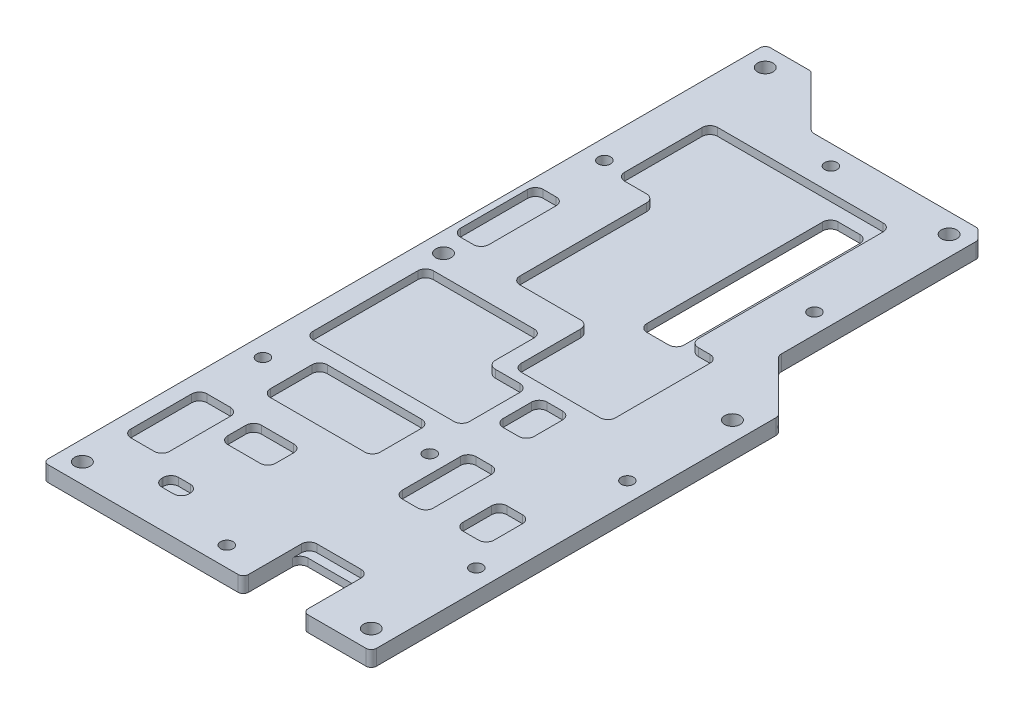
SolidWorks part; units mm, degrees
ref_plane "Front Plane" through (0, 0, 0) normal (0, 0, 1) x (1, 0, 0)
ref_plane "Top Plane" through (0, 0, 0) normal (0, 1, 0) x (1, 0, 0)
ref_plane "Right Plane" through (0, 0, 0) normal (1, 0, 0) x (0, 0, -1)
sketch "Sketch1" plane through (0, 0, 0) normal (0, 1, 0) x (1, 0, 0)
  line L0 (0, 1) -> (0, 138.7)
  line L1 (1, 0) -> (37.75, 0)
  line L2 (63.5, 1) -> (63.5, 78.3258)
  line L3 (1, 139.7) -> (8.4758, 139.7)
  line L4 (19.6713, 129.54) -> (50.8958, 129.54)
  line L5 (9.1829, 139.4071) -> (18.6107, 129.9793)
  line L6 (53.34, 89.5213) -> (53.34, 127.0958)
  line L7 (63.2071, 79.0329) -> (53.7793, 88.4607)
  line L8 (51.6029, 129.2471) -> (53.0471, 127.8029)
  line L13 (38.75, 1) -> (38.75, 9.5)
  line L14 (40.25, 11) -> (48.75, 11)
  line L15 (50.25, 9.5) -> (50.25, 1)
  line L16 (51.25, 0) -> (62.5, 0)
  arc A2 (1, 0) -> (0, 1) centre (1, 1) cw
  arc A3 (63.5, 1) -> (62.5, 0) centre (62.5, 1) cw
  arc A4 (53.7793, 88.4607) -> (53.34, 89.5213) centre (54.84, 89.5213) cw
  arc A5 (18.6107, 129.9793) -> (19.6713, 129.54) centre (19.6713, 131.04) ccw
  arc A6 (63.5, 78.3258) -> (63.2071, 79.0329) centre (62.5, 78.3258) ccw
  arc A7 (53.34, 127.0958) -> (53.0471, 127.8029) centre (52.34, 127.0958) ccw
  arc A8 (51.6029, 129.2471) -> (50.8958, 129.54) centre (50.8958, 128.54) ccw
  arc A9 (9.1829, 139.4071) -> (8.4758, 139.7) centre (8.4758, 138.7) ccw
  arc A10 (1, 139.7) -> (0, 138.7) centre (1, 138.7) ccw
  arc A13 (48.75, 11) -> (50.25, 9.5) centre (48.75, 9.5) cw
  arc A14 (38.75, 9.5) -> (40.25, 11) centre (40.25, 9.5) cw
  arc A15 (50.25, 1) -> (51.25, 0) centre (51.25, 1) ccw
  arc A16 (38.75, 1) -> (37.75, 0) centre (37.75, 1) cw
  point P20 (0, 0)
  point P23 (63.5, 0)
  point P26 (53.34, 88.9)
  point P29 (19.05, 129.54)
  point P32 (63.5, 78.74)
  point P35 (53.34, 127.51)
  point P38 (51.31, 129.54)
  point P41 (8.89, 139.7)
  point P44 (0, 139.7)
  point P45 (38.75, 11)
  point P48 (50.25, 0)
  point P51 (38.75, 0)
  dimension "D14" = 1.5
  dimension "D15" = 1
  dimension "D16" = 1
  dimension "D17" = 1.5
  dimension "D18" = 1
  dimension "D19" = 1
  dimension "D1" = 139.7
  dimension "D2" = 63.5
  dimension "D3" = 78.74
  dimension "D4" = 8.89
  dimension "D5" = 10.16
  dimension "D6" = 10.16
  dimension "D7" = 32.26
  dimension "D8" = 10.16
  dimension "D9" = 10.16
  dimension "D10" = 2.03
  dimension "D11" = 13.25
  dimension "D12" = 11.5
  dimension "D13" = 11
extrude "Boss-Extrude1" add sketch "Sketch1" along normal blind 3
sketch "Sketch2" plane through (0, 3, 0) normal (0, 1, 0) x (1, 0, 0)
  line L36 (50.25, 0) -> (50.25, 11.25)
  line L37 (51.25, 0) -> (62.5, 0) construction
  line L38 (48.75, 12.75) -> (40.25, 12.75)
  line L39 (38.75, 11.25) -> (38.75, 0)
  line L40 (1, 0) -> (37.75, 0) construction
  line L41 (38.75, 0) -> (50.25, 0)
  line L42 (63.5, 1) -> (63.5, 78.3258) construction
  line L43 (0, 138.7) -> (0, 1) construction
  line L44 (52.25, 37.5) -> (55.25, 37.5)
  line L45 (50.75, 36) -> (50.75, 30.5)
  line L46 (52.25, 29) -> (55.25, 29)
  line L47 (56.75, 36) -> (56.75, 30.5)
  line L48 (41, 42.75) -> (44, 42.75)
  line L49 (39.5, 41.25) -> (39.5, 30)
  line L50 (41, 28.5) -> (44, 28.5)
  line L51 (45.5, 41.25) -> (45.5, 30)
  line L52 (11.25, 43.75) -> (29.5, 43.75)
  line L53 (9.75, 42.25) -> (9.75, 34.25)
  line L54 (11.25, 32.75) -> (29.5, 32.75)
  line L55 (31, 42.25) -> (31, 34.25)
  line L56 (18, 10.5) -> (15.75, 10.5)
  line L57 (19.5, 9) -> (19.5, 8.75)
  line L58 (18, 7.25) -> (15.75, 7.25)
  line L59 (14.25, 9) -> (14.25, 8.75)
  line L60 (4.25, 68.25) -> (4.25, 48)
  line L61 (4.5, 27.25) -> (9, 27.25)
  line L62 (3, 25.75) -> (3, 14)
  line L63 (4.5, 12.5) -> (9, 12.5)
  line L64 (10.5, 25.75) -> (10.5, 14)
  line L65 (15, 27.25) -> (21.25, 27.25)
  line L66 (13.5, 25.75) -> (13.5, 22.25)
  line L67 (15, 20.75) -> (21.25, 20.75)
  line L68 (22.75, 25.75) -> (22.75, 22.25)
  line L69 (5.75, 46.5) -> (33, 46.5)
  line L70 (34.5, 48) -> (34.5, 57.75)
  line L71 (33, 59.25) -> (28.25, 59.25)
  line L72 (26.75, 60.75) -> (26.75, 68.25)
  line L73 (25.25, 69.75) -> (5.75, 69.75)
  line L74 (31.25, 61.25) -> (46.5, 61.25)
  line L75 (38.75, 58.75) -> (41.75, 58.75)
  line L76 (37.25, 57.25) -> (37.25, 51.75)
  line L77 (38.75, 50.25) -> (41.75, 50.25)
  line L78 (43.25, 57.25) -> (43.25, 51.75)
  line L79 (48, 62.75) -> (48, 81)
  line L80 (46.5, 82.5) -> (44.25, 82.5)
  line L81 (42.75, 84) -> (42.75, 119.75)
  line L82 (41.25, 121.25) -> (9.25, 121.25)
  line L83 (7.75, 119.75) -> (7.75, 104.75)
  line L84 (9.25, 103.25) -> (13.5, 103.25)
  line L85 (15, 101.75) -> (15, 77.25)
  line L86 (16.5, 75.75) -> (28.25, 75.75)
  line L87 (29.75, 74.25) -> (29.75, 62.75)
  line L89 (2.75, 94) -> (5.25, 94)
  line L90 (1.25, 92.5) -> (1.25, 79.5)
  line L91 (2.75, 78) -> (5.25, 78)
  line L92 (6.75, 92.5) -> (6.75, 79.5)
  arc A32 (50.25, 11.25) -> (48.75, 12.75) centre (48.75, 11.25) ccw
  arc A33 (40.25, 12.75) -> (38.75, 11.25) centre (40.25, 11.25) ccw
  arc A34 (50.75, 30.5) -> (52.25, 29) centre (52.25, 30.5) ccw
  arc A35 (55.25, 29) -> (56.75, 30.5) centre (55.25, 30.5) ccw
  arc A36 (56.75, 36) -> (55.25, 37.5) centre (55.25, 36) ccw
  arc A37 (50.75, 36) -> (52.25, 37.5) centre (52.25, 36) cw
  arc A38 (39.5, 30) -> (41, 28.5) centre (41, 30) ccw
  arc A39 (44, 28.5) -> (45.5, 30) centre (44, 30) ccw
  arc A40 (44, 42.75) -> (45.5, 41.25) centre (44, 41.25) cw
  arc A41 (41, 42.75) -> (39.5, 41.25) centre (41, 41.25) ccw
  arc A42 (29.5, 43.75) -> (31, 42.25) centre (29.5, 42.25) cw
  arc A43 (29.5, 32.75) -> (31, 34.25) centre (29.5, 34.25) ccw
  arc A44 (9.75, 34.25) -> (11.25, 32.75) centre (11.25, 34.25) ccw
  arc A45 (11.25, 43.75) -> (9.75, 42.25) centre (11.25, 42.25) ccw
  arc A46 (19.5, 8.75) -> (18, 7.25) centre (18, 8.75) cw
  arc A47 (18, 10.5) -> (19.5, 9) centre (18, 9) cw
  arc A48 (15.75, 7.25) -> (14.25, 8.75) centre (15.75, 8.75) cw
  arc A49 (15.75, 10.5) -> (14.25, 9) centre (15.75, 9) ccw
  arc A50 (21.25, 20.75) -> (22.75, 22.25) centre (21.25, 22.25) ccw
  arc A51 (21.25, 27.25) -> (22.75, 25.75) centre (21.25, 25.75) cw
  arc A52 (15, 27.25) -> (13.5, 25.75) centre (15, 25.75) ccw
  arc A53 (13.5, 22.25) -> (15, 20.75) centre (15, 22.25) ccw
  arc A54 (3, 14) -> (4.5, 12.5) centre (4.5, 14) ccw
  arc A55 (9, 12.5) -> (10.5, 14) centre (9, 14) ccw
  arc A56 (9, 27.25) -> (10.5, 25.75) centre (9, 25.75) cw
  arc A57 (4.5, 27.25) -> (3, 25.75) centre (4.5, 25.75) ccw
  arc A58 (26.75, 68.25) -> (25.25, 69.75) centre (25.25, 68.25) ccw
  arc A59 (34.5, 57.75) -> (33, 59.25) centre (33, 57.75) ccw
  arc A60 (33, 46.5) -> (34.5, 48) centre (33, 48) ccw
  arc A61 (4.25, 48) -> (5.75, 46.5) centre (5.75, 48) ccw
  arc A62 (5.75, 69.75) -> (4.25, 68.25) centre (5.75, 68.25) ccw
  arc A63 (28.25, 59.25) -> (26.75, 60.75) centre (28.25, 60.75) cw
  arc A64 (41.75, 58.75) -> (43.25, 57.25) centre (41.75, 57.25) cw
  arc A65 (41.75, 50.25) -> (43.25, 51.75) centre (41.75, 51.75) ccw
  arc A66 (37.25, 51.75) -> (38.75, 50.25) centre (38.75, 51.75) ccw
  arc A67 (38.75, 58.75) -> (37.25, 57.25) centre (38.75, 57.25) ccw
  arc A68 (42.75, 119.75) -> (41.25, 121.25) centre (41.25, 119.75) ccw
  arc A69 (44.25, 82.5) -> (42.75, 84) centre (44.25, 84) cw
  arc A70 (48, 81) -> (46.5, 82.5) centre (46.5, 81) ccw
  arc A71 (46.5, 61.25) -> (48, 62.75) centre (46.5, 62.75) ccw
  arc A72 (31.25, 61.25) -> (29.75, 62.75) centre (31.25, 62.75) cw
  arc A73 (28.25, 75.75) -> (29.75, 74.25) centre (28.25, 74.25) cw
  arc A74 (15, 77.25) -> (16.5, 75.75) centre (16.5, 77.25) ccw
  arc A75 (13.5, 103.25) -> (15, 101.75) centre (13.5, 101.75) cw
  arc A76 (7.75, 104.75) -> (9.25, 103.25) centre (9.25, 104.75) ccw
  arc A77 (9.25, 121.25) -> (7.75, 119.75) centre (9.25, 119.75) ccw
  arc A78 (1.25, 79.5) -> (2.75, 78) centre (2.75, 79.5) ccw
  arc A79 (5.25, 78) -> (6.75, 79.5) centre (5.25, 79.5) ccw
  arc A80 (5.25, 94) -> (6.75, 92.5) centre (5.25, 92.5) cw
  arc A81 (2.75, 94) -> (1.25, 92.5) centre (2.75, 92.5) ccw
  point P12 (50.25, 12.75)
  point P15 (38.75, 12.75)
  point P22 (50.75, 29)
  point P25 (56.75, 29)
  point P28 (56.75, 37.5)
  point P37 (39.5, 28.5)
  point P40 (45.5, 28.5)
  point P43 (45.5, 42.75)
  point P56 (31, 32.75)
  point P59 (9.75, 32.75)
  point P62 (9.75, 43.75)
  point P69 (19.5, 7.25)
  point P72 (19.5, 10.5)
  point P77 (14.25, 10.5)
  point P90 (22.75, 27.25)
  point P93 (13.5, 27.25)
  point P96 (13.5, 20.75)
  point P99 (3, 12.5)
  point P104 (10.5, 27.25)
  point P107 (3, 27.25)
  point P117 (26.75, 69.75)
  point P120 (34.5, 59.25)
  point P123 (34.5, 46.5)
  point P126 (4.25, 46.5)
  point P129 (4.25, 69.75)
  point P137 (43.25, 58.75)
  point P142 (37.25, 50.25)
  point P145 (37.25, 58.75)
  point P158 (42.75, 121.25)
  point P161 (42.75, 82.5)
  point P164 (48, 82.5)
  point P167 (48, 61.25)
  point P170 (29.75, 61.25)
  point P175 (15, 75.75)
  point P178 (15, 103.25)
  point P181 (7.75, 103.25)
  point P184 (7.75, 121.25)
  point P192 (1.25, 78)
  point P197 (6.75, 94)
  point P200 (1.25, 94)
  dimension "D35" = 30.25
  dimension "D36" = 12.75
  dimension "D37" = 22.5
  dimension "D38" = 4.25
  dimension "D39" = 46.5
  dimension "D40" = 1.5
  dimension "D41" = 1.5
  dimension "D42" = 8.5
  dimension "D4" = 1.5
  dimension "D9" = 1.5
  dimension "D14" = 1.5
  dimension "D19" = 1.5
  dimension "D24" = 1.5
  dimension "D33" = 1.5
  dimension "D46" = 1.5
  dimension "D57" = 1.5
  dimension "D62" = 1.5
  dimension "D1" = 13.25
  dimension "D2" = 12.75
  dimension "D3" = 11.5
  dimension "D5" = 6
  dimension "D6" = 8.5
  dimension "D7" = 6.75
  dimension "D8" = 29
  dimension "D10" = 14.25
  dimension "D11" = 6
  dimension "D12" = 18
  dimension "D13" = 28.5
  dimension "D15" = 21.25
  dimension "D16" = 11
  dimension "D17" = 32.75
  dimension "D18" = 9.75
  dimension "D20" = 3.25
  dimension "D21" = 5.25
  dimension "D22" = 7.25
  dimension "D23" = 14.25
  dimension "D25" = 14.75
  dimension "D26" = 7.5
  dimension "D27" = 12.5
  dimension "D28" = 3
  dimension "D29" = 6.5
  dimension "D30" = 9.25
  dimension "D31" = 13.5
  dimension "D32" = 20.75
  dimension "D34" = 23.25
  dimension "D43" = 6
  dimension "D44" = 20.25
  dimension "D45" = 50.25
  dimension "D47" = 18.25
  dimension "D48" = 21.25
  dimension "D49" = 5.25
  dimension "D50" = 38.75
  dimension "D51" = 35
  dimension "D52" = 18
  dimension "D53" = 7.25
  dimension "D54" = 27.5
  dimension "D55" = 15.5
  dimension "D56" = 61.25
  dimension "D58" = 16
  dimension "D59" = 5.5
  dimension "D60" = 1.25
  dimension "D61" = 78
extrude "Cut-Extrude1" cut sketch "Sketch2" against normal blind 1.5
sketch "Sketch3" plane through (0, 0, 0) normal (0, -1, 0) x (-1, 0, 0)
  line L0 (-37.34, 118.58) -> (-37.34, 81.58) construction
  line L1 (-39.44, 118.58) -> (-35.24, 118.58)
  line L2 (-40.94, 117.08) -> (-40.94, 83.08)
  line L3 (-39.44, 81.58) -> (-35.24, 81.58)
  line L4 (-33.74, 117.08) -> (-33.74, 83.08)
  line L5 (-40.94, 100.08) -> (-33.74, 100.08) construction
  arc A0 (-40.94, 83.08) -> (-39.44, 81.58) centre (-39.44, 83.08) ccw
  arc A1 (-35.24, 81.58) -> (-33.74, 83.08) centre (-35.24, 83.08) ccw
  arc A2 (-35.24, 118.58) -> (-33.74, 117.08) centre (-35.24, 117.08) cw
  arc A3 (-39.44, 118.58) -> (-40.94, 117.08) centre (-39.44, 117.08) ccw
  point P12 (-40.94, 81.58)
  point P17 (-33.74, 118.58)
  point P20 (-40.94, 118.58)
  dimension "D5" = 1.5
  dimension "D1" = 37
  dimension "D2" = 7.2
  dimension "D3" = 37.34
  dimension "D4" = 100.08
extrude "Cut-Extrude2" cut sketch "Sketch3" against normal up to next
hole_wizard "Ø3.0mm Dowel Hole1" positions "Sketch5" profile "Sketch6" hole size "Ø3.0" standard "ISO" end condition through all
sketch "Sketch5" plane through (0, 3, 0) normal (0, 1, 0) x (1, 0, 0)
  line L0 (51.25, 0) -> (62.5, 0) construction
  line L1 (63.5, 1) -> (63.5, 78.3258) construction
  line L2 (53.34, 89.5213) -> (53.34, 127.0958) construction
  line L3 (50.8958, 129.54) -> (19.6713, 129.54) construction
  line L4 (0, 138.7) -> (0, 1) construction
  line L5 (8.4758, 139.7) -> (1, 139.7) construction
  line L6 (1, 0) -> (37.75, 0) construction
  point P0 (3.81, 135.89)
  point P2 (49.53, 125.73)
  point P4 (59.69, 73.66)
  point P6 (59.69, 3.81)
  point P8 (3.81, 3.81)
  point P10 (3.81, 73.66)
  dimension "D1" = 3.81
  dimension "D2" = 3.81
  dimension "D3" = 3.81
  dimension "D4" = 3.81
  dimension "D5" = 3.81
  dimension "D6" = 3.81
  dimension "D7" = 3.81
  dimension "D8" = 3.81
  dimension "D9" = 3.81
  dimension "D10" = 3.81
  dimension "D11" = 69.85
  dimension "D12" = 69.85
sketch "Sketch6" plane through (3.81, 3, -135.89) normal (1, 0, 0) x (0, 0, 1)
  line L0 (0, 0) -> (0, 3)
  line L1 (0, 3) -> (1.5, 3)
  line L2 (1.5, 3) -> (1.5, 0)
  line L5 (1.5, 0) -> (0, 0)
  line L11 (0, -6.35) -> (0, 107.95) construction
  dimension "Thru Hole Dia." = 3
  dimension "Thru Hole Depth" = 3
hole_wizard "CSK for M2 Countersunk Flat Head Screw1" positions "Sketch7" profile "Sketch8" countersink size "M2" standard "DIN" end condition through all
sketch "Sketch7" plane through (0, 0, 0) normal (0, -1, 0) x (-1, 0, 0)
  line L0 (0, 138.7) -> (0, 1) construction
  line L1 (-50.8958, 129.54) -> (-19.6713, 129.54) construction
  line L2 (-1, 0) -> (-37.75, 0) construction
  line L3 (-63.5, 1) -> (-63.5, 78.3258) construction
  line L4 (-53.34, 89.5213) -> (-53.34, 127.0958) construction
  circle A0 centre (-59.69, 3.81) radius 1.5 construction
  circle A2 centre (-3.81, 3.81) radius 1.5 construction
  circle A3 centre (-3.81, 135.89) radius 1.5 construction
  circle A4 centre (-49.53, 125.73) radius 1.5 construction
  point P0 (-26.67, 125.73)
  point P2 (-31.75, 3.81)
  point P4 (-59.69, 53.34)
  point P6 (-3.81, 38.74)
  point P8 (-36.07, 38.74)
  point P10 (-59.69, 24.13)
  point P12 (-49.53, 99.69)
  point P14 (-3.81, 104.77)
  point P27 (-59.69, 59.3288)
  point P28 (-3.81, 41.433)
  point P29 (-59.69, 26.4527)
  point P36 (0, 0)
  dimension "D1" = 3.81
  dimension "D2" = 3.81
  dimension "D3" = 3.81
  dimension "D4" = 3.81
  dimension "D5" = 3.81
  dimension "D6" = 3.81
  dimension "D7" = 3.81
  dimension "D8" = 49.53
  dimension "D9" = 20.32
  dimension "D10" = 32.26
  dimension "D11" = 27.94
  dimension "D12" = 34.93
  dimension "D13" = 31.12
  dimension "D14" = 26.04
  dimension "D15" = 22.86
sketch "Sketch8" plane through (26.67, 0, -125.73) normal (1, 0, 0) x (0, 0, -1)
  line L0 (0, 0) -> (0, 3)
  line L1 (0, 3) -> (1.2, 3)
  line L2 (1.2, 3) -> (1.2, 1)
  line L3 (1.2, 1) -> (2.2, 0)
  line L5 (2.2, 0) -> (0, 0)
  line L6 (-1.2, 1) -> (-2.2, 0) construction
  line L11 (0, -6.35) -> (0, 107.95) construction
  dimension "Thru Hole Dia." = 2.4
  dimension "Thru Hole Depth" = 3
  dimension "Near C'Sink Dia." = 4.4
  dimension "Near C'Sink Angle" = 90
